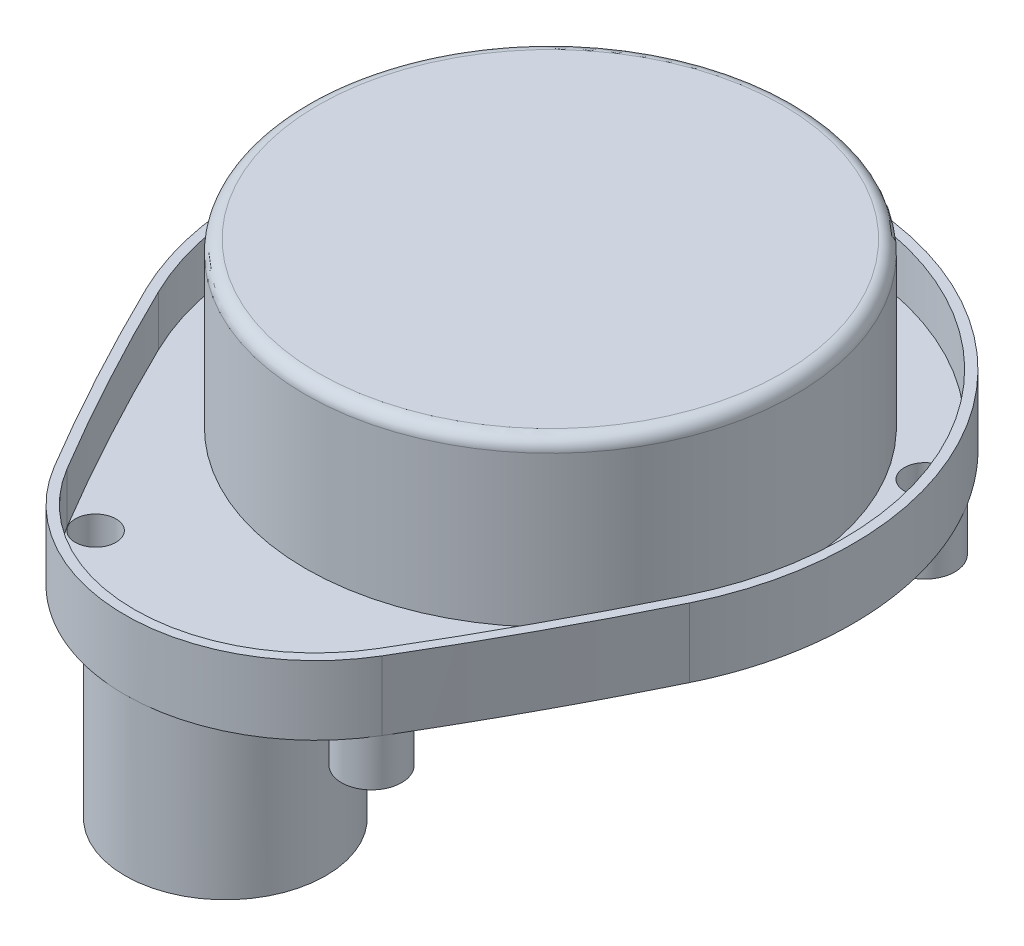
SolidWorks part; units mm, degrees
material "ABS"
ref_plane "Front Plane" through (0, 0, 0) normal (0, 0, 1) x (1, 0, 0)
ref_plane "Top Plane" through (0, 0, 0) normal (0, 1, 0) x (1, 0, 0)
ref_plane "Right Plane" through (0, 0, 0) normal (1, 0, 0) x (0, 0, -1)
sketch "Sketch1" plane through (0, 0, 0) normal (0, 1, 0) x (1, 0, 0)
  line L0 (0, 48.2) -> (0, -67.8) construction
  line L1 (0, -67.8) -> (21.7641, -67.8) construction
  line L3 (37, 22.6839) -> (0, 22.6839) construction
  line L4 (22, -50.494) -> (0, -50.494) construction
  circle A0 centre (0, 0) radius 48.2 construction
  circle A1 centre (37, 22.6839) radius 4.8
  circle A2 centre (22, -50.494) radius 4.8
  circle A3 centre (-37, 22.6839) radius 4.8
  circle A4 centre (-22, -50.494) radius 4.8
  arc A5 (26.1244, -52.9494) -> (-26.1244, -52.9494) centre (0, -37.3963) cw
  arc A6 (-26.1244, -52.9494) -> (-43.317, -21.1395) centre (348.4365, 170.0439) cw
  arc A7 (-43.317, -21.1395) -> (0, 48.2) centre (0, 0) cw
  arc A8 (43.317, -21.1395) -> (0, 48.2) centre (0, 0) ccw
  arc A9 (26.1244, -52.9494) -> (43.317, -21.1395) centre (-348.4365, 170.0439) ccw
  dimension "D1" = 96.4
  dimension "D2" = 9.6
  dimension "D4" = 37
  dimension "D3" = 116
  dimension "D5" = 22
  dimension "D6" = 94
extrude "Boss-Extrude2" add sketch "Sketch1" along normal blind 3 contours A7 A8 A9 A5 A6
sketch "Sketch3" plane through (0, 0, 0) normal (0, -1, 0) x (1, 0, 0)
  circle A1 centre (-37, -22.6839) radius 4.8
  circle A2 centre (-37, -22.6839) radius 4.8
  circle A3 centre (22, 50.494) radius 4.8
  arc A4 (-26.1244, 52.9494) -> (-43.317, 21.1395) centre (348.4365, -170.0439) ccw
  arc A5 (-43.317, 21.1395) -> (43.317, 21.1395) centre (0, 0) ccw
  arc A6 (43.317, 21.1395) -> (26.1244, 52.9494) centre (-348.4365, -170.0439) ccw
  arc A7 (26.1244, 52.9494) -> (-26.1244, 52.9494) centre (0, 37.3963) ccw
  arc A8 (-26.1244, 52.9494) -> (-43.317, 21.1395) centre (348.4365, -170.0439) ccw
  arc A9 (-43.317, 21.1395) -> (43.317, 21.1395) centre (0, 0) ccw
  arc A10 (43.317, 21.1395) -> (26.1244, 52.9494) centre (-348.4365, -170.0439) ccw
  arc A11 (26.1244, 52.9494) -> (-26.1244, 52.9494) centre (0, 37.3963) ccw
  circle A12 centre (22, 50.494) radius 4.8
  circle A13 centre (37, -22.6839) radius 4.8
  circle A14 centre (37, -22.6839) radius 4.8
  circle A15 centre (-22, 50.494) radius 4.8
  circle A16 centre (-22, 50.494) radius 4.8
  arc A19 (26.1244, 52.9494) -> (-26.1244, 52.9494) centre (0, 37.3963) ccw
  arc A20 (-26.1244, 52.9494) -> (-43.317, 21.1395) centre (348.4365, -170.0439) ccw
  arc A21 (-43.317, 21.1395) -> (0, -48.2) centre (0, 0) ccw
  arc A22 (0, -48.2) -> (43.317, 21.1395) centre (0, 0) ccw
  arc A23 (43.317, 21.1395) -> (26.1244, 52.9494) centre (-348.4365, -170.0439) ccw
  arc A24 (26.1244, 52.9494) -> (-26.1244, 52.9494) centre (0, 37.3963) ccw
  arc A25 (-26.1244, 52.9494) -> (-43.317, 21.1395) centre (348.4365, -170.0439) ccw
  arc A26 (-43.317, 21.1395) -> (0, -48.2) centre (0, 0) ccw
  arc A27 (0, -48.2) -> (43.317, 21.1395) centre (0, 0) ccw
  arc A28 (43.317, 21.1395) -> (26.1244, 52.9494) centre (-348.4365, -170.0439) ccw
  dimension "D1" = 0
  dimension "D2" = 0
  dimension "D3" = 0
  dimension "D4" = 0
  dimension "D5" = 0
  dimension "D6" = 0
extrude "Boss-Extrude3" add sketch "Sketch3" along normal blind 7.4 contours A14 | A2 | A16 | A12 region at (-37, 0, -22.6839) region at (37, 0, -22.6839) region at (22, 0, 50.494) region at (-22, 0, 50.494)
sketch "Sketch6" plane through (0, 0, 0) normal (0, -1, 0) x (1, 0, 0)
  line L0 (0, 67.8) -> (0, 51.8) construction
  arc A0 (26.1244, 52.9494) -> (-26.1244, 52.9494) centre (0, 37.3963) ccw construction
  circle A1 centre (0, 51.8) radius 16
  dimension "D1" = 32
extrude "Boss-Extrude6" add sketch "Sketch6" along normal blind 25
sketch "Sketch4" plane through (0, 0, 0) normal (0, -1, 0) x (1, 0, 0)
  circle A0 centre (0, 0) radius 38.5
  dimension "D1" = 77
extrude "Boss-Extrude4" add sketch "Sketch4" along normal blind 6
sketch "Sketch5" plane through (0, -6, 0) normal (0, -1, 0) x (1, 0, 0)
  circle A0 centre (0, 0) radius 28.2
  dimension "D1" = 56.4
extrude "Boss-Extrude5" add sketch "Sketch5" along normal blind 1.4
chamfer "Chamfer1" distance 1.4 angle 45 1 edges at (0, -7.4, -28.2)
fillet "Fillet2" radius 2 1 edges at (0, -6, -38.5)
sketch "Sketch7" plane through (0, -7.4, 0) normal (0, -1, 0) x (1, 0, 0)
  circle A0 centre (37, -22.6839) radius 3.25
  circle A1 centre (-37, -22.6839) radius 3.25
  circle A2 centre (-22, 50.494) radius 3.25
  circle A3 centre (22, 50.494) radius 3.25
  dimension "D1" = 6.5
extrude "Cut-Extrude1" cut sketch "Sketch7" against normal blind 2
chamfer "Chamfer2" distance 0.5 angle 45 4 edges at (37, -7.4, -25.9339) (-37, -7.4, -25.9339) (-22, -7.4, 47.244) (22, -7.4, 47.244)
sketch "Sketch9" plane through (0, -5.4, 0) normal (0, -1, 0) x (1, 0, 0)
  circle A0 centre (22, 50.494) radius 1.5
  circle A1 centre (-22, 50.494) radius 1.5
  circle A2 centre (-37, -22.6839) radius 1.5
  circle A3 centre (37, -22.6839) radius 1.5
  dimension "D1" = 3
extrude "Cut-Extrude2" cut sketch "Sketch9" against normal through all
sketch "Sketch10" plane through (0, 3, 0) normal (0, 1, 0) x (1, 0, 0)
  arc A0 (24.8355, -52.1821) -> (41.9689, -20.4817) centre (-348.4365, 170.0439) ccw
  arc A1 (41.9689, -20.4817) -> (-41.9689, -20.4817) centre (0, 0) ccw
  arc A2 (-41.9689, -20.4817) -> (-24.8355, -52.1821) centre (348.4365, 170.0439) ccw
  arc A3 (-24.8355, -52.1821) -> (24.8355, -52.1821) centre (0, -37.3963) ccw
  arc A4 (-43.317, -21.1395) -> (-26.1244, -52.9494) centre (348.4365, 170.0439) ccw
  arc A5 (-26.1244, -52.9494) -> (26.1244, -52.9494) centre (0, -37.3963) ccw
  arc A6 (26.1244, -52.9494) -> (43.317, -21.1395) centre (-348.4365, 170.0439) ccw
  arc A7 (43.317, -21.1395) -> (-43.317, -21.1395) centre (0, 0) ccw
  arc A8 (-43.317, -21.1395) -> (-26.1244, -52.9494) centre (348.4365, 170.0439) ccw
  arc A9 (-26.1244, -52.9494) -> (26.1244, -52.9494) centre (0, -37.3963) ccw
  arc A10 (26.1244, -52.9494) -> (43.317, -21.1395) centre (-348.4365, 170.0439) ccw
  arc A11 (43.317, -21.1395) -> (-43.317, -21.1395) centre (0, 0) ccw
  arc A12 (26.1244, -52.9494) -> (43.317, -21.1395) centre (-348.4365, 170.0439) ccw construction
  arc A19 (-26.1244, -52.9494) -> (26.1244, -52.9494) centre (0, -37.3963) ccw
  arc A20 (-43.317, -21.1395) -> (-26.1244, -52.9494) centre (348.4365, 170.0439) ccw
  arc A21 (0, 48.2) -> (-43.317, -21.1395) centre (0, 0) ccw
  arc A22 (43.317, -21.1395) -> (0, 48.2) centre (0, 0) ccw
  arc A23 (26.1244, -52.9494) -> (43.317, -21.1395) centre (-348.4365, 170.0439) ccw
  arc A24 (-26.1244, -52.9494) -> (26.1244, -52.9494) centre (0, -37.3963) ccw
  arc A25 (-43.317, -21.1395) -> (-26.1244, -52.9494) centre (348.4365, 170.0439) ccw
  arc A26 (0, 48.2) -> (-43.317, -21.1395) centre (0, 0) ccw
  arc A27 (43.317, -21.1395) -> (0, 48.2) centre (0, 0) ccw
  arc A28 (26.1244, -52.9494) -> (43.317, -21.1395) centre (-348.4365, 170.0439) ccw
  arc M18 (-43.317, -21.1395) -> (-26.1244, -52.9494) centre (348.4365, 170.0439) ccw
  arc M19 (-26.1244, -52.9494) -> (26.1244, -52.9494) centre (0, -37.3963) ccw
  arc M20 (26.1244, -52.9494) -> (43.317, -21.1395) centre (-348.4365, 170.0439) ccw
  arc M21 (43.317, -21.1395) -> (-43.317, -21.1395) centre (0, 0) ccw
  dimension "D1" = 0
  dimension "D2" = 1.5
  dimension "D5" = 0
extrude "Boss-Extrude7" add sketch "Sketch10" along normal blind 8 contours A11 A3 A2 A1 A0 M21 M18 M19 M20 region at (-40.751, 3, -25.4575)
sketch "Sketch14" plane through (0, 3, 0) normal (0, 1, 0) x (1, 0, 0)
  circle A0 centre (-37, 22.6839) radius 3.25
  circle A1 centre (37, 22.6839) radius 3.25
  circle A2 centre (22, -50.494) radius 3.25
  circle A3 centre (-22, -50.494) radius 3.25
  dimension "D1" = 6.5
extrude "Cut-Extrude3" cut sketch "Sketch14" against normal blind 6
sketch "Sketch15" plane through (0, 3, 0) normal (0, 1, 0) x (1, 0, 0)
  circle A0 centre (0, 0) radius 39
  dimension "D1" = 78
extrude "Boss-Extrude8" add sketch "Sketch15" along normal blind 26
fillet "Fillet3" radius 2 1 edges at (0, 29, 39)
ref_plane "Plane1" through (0, 20, 0) normal (0, 1, 0) x (1, 0, 0)
sketch "Sketch16" plane through (0, 20, 0) normal (0, 1, 0) x (1, 0, 0)
  line L0 (0, 0) -> (0, 37) construction
  circle A0 centre (0, 0) radius 37 construction
